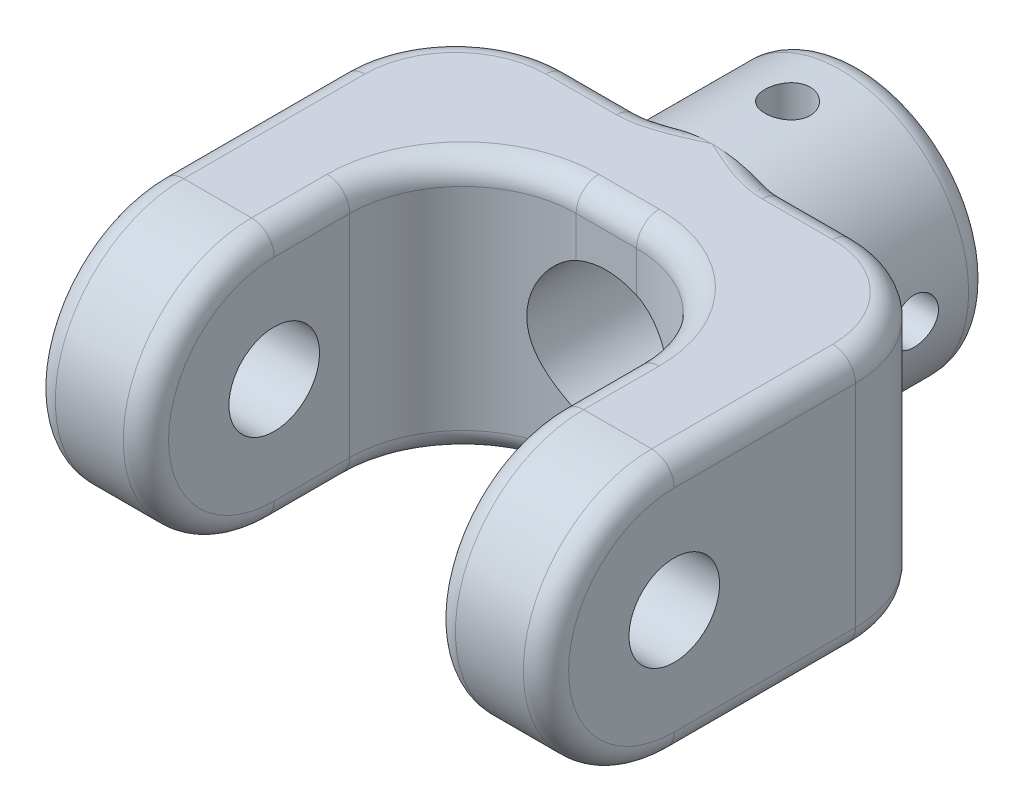
SolidWorks part; units mm, degrees
ref_plane "前视基准面" through (0, 0, 0) normal (0, 0, 1) x (1, 0, 0)
ref_plane "上视基准面" through (0, 0, 0) normal (0, 1, 0) x (1, 0, 0)
ref_plane "右视基准面" through (0, 0, 0) normal (1, 0, 0) x (0, 0, -1)
other "Configuration Table"
sketch "草图1" plane through (0, 0, 0) normal (0, 1, 0) x (1, 0, 0)
  line L0 (-768.9064, 0) -> (37676.4149, 0) construction
  line L1 (-17, 0) -> (17, 0)
  line L2 (17, 0) -> (17, -20)
  line L3 (0, -1000) -> (0, 49000) construction
  line L4 (17, -20) -> (19, -20)
  line L5 (34, -35) -> (34, -76)
  line L6 (34, -76) -> (19, -76)
  line L7 (19, -76) -> (19, -49)
  line L8 (-17, 0) -> (-17, -20)
  line L9 (-17, -20) -> (-19, -20)
  line L10 (-34, -76) -> (-19, -76)
  line L11 (-19, -76) -> (-19, -49)
  line L12 (-34, -35) -> (-34, -76)
  line L13 (-4, -34) -> (4, -34)
  arc A0 (19, -49) -> (4, -34) centre (4, -49) ccw
  arc A1 (-19, -49) -> (-4, -34) centre (-4, -49) cw
  arc A2 (34, -35) -> (19, -20) centre (19, -35) ccw
  arc A3 (-34, -35) -> (-19, -20) centre (-19, -35) cw
  point P6 (0, 0)
  dimension "D7" = 30
  dimension "D8" = 30
  dimension "D1" = 34
  dimension "D2" = 20
  dimension "D3" = 56
  dimension "D4" = 34
  dimension "D5" = 15
  dimension "D6" = 42
extrude "凸台-拉伸1" add sketch "草图1" along normal blind 34
sketch "草图3" plane through (0, 0, 0) normal (0, 0, 1) x (1, 0, 0)
  line L0 (-17, 34) -> (17, 0) construction
  line L5 (-17, 0) -> (17, 0)
  line L6 (-17, 34) -> (-17, 0)
  line L7 (17, 34) -> (-17, 34)
  line L8 (17, 0) -> (17, 34)
  line L9 (-17, 0) -> (17, 0)
  line L10 (-17, 34) -> (-17, 0)
  line L11 (17, 34) -> (-17, 34)
  line L12 (17, 0) -> (17, 34)
  circle A0 centre (0, 17) radius 17
  dimension "D1" = 0
extrude "切除-拉伸1" cut sketch "草图3" along normal up to surface (20 mm away) contours A0 L10 L9 | L0 L10 A0 | L11 L0 A0 | A0 L12 L11 | A0 L0 L12 | L0 A0 L9 region at (-10.9375, 32.468, 0) region at (-15.468, 27.9375, 0) region at (-13.2027, 3.7973, 0) region at (13.2027, 30.2027, 0) region at (15.468, 6.0625, 0) region at (10.9375, 1.532, 0) up to face at (18, 17, 20)
sketch "草图5" plane through (0, 0, 0) normal (0, 0, 1) x (1, 0, 0)
  circle A0 centre (0, 17) radius 9.5
  dimension "D1" = 19
extrude "切除-拉伸2" cut sketch "草图5" along normal through all contours A0
sketch "草图6" plane through (0, 0, 0) normal (1, 0, 0) x (0, 0, -1)
  line L4 (-76, 0) -> (-35, 0)
  line L5 (-35, 0) -> (-35, 34)
  line L6 (-35, 34) -> (-76, 34)
  line L7 (-76, 34) -> (-76, 0)
  line L8 (-76, 0) -> (-59, 0)
  line L10 (-59, 34) -> (-76, 34)
  line L11 (-76, 34) -> (-76, 0)
  arc A0 (-59, 34) -> (-59, 0) centre (-59, 17) ccw
  dimension "D1" = 0
extrude "切除-拉伸3" cut sketch "草图6" against normal through all and the other way through all contours A0 L10 L11 | A0 L11 L8 region at (0, 3.7973, 72.2027) region at (0, 30.2027, 72.2027)
sketch "草图7" plane through (0, 0, 0) normal (1, 0, 0) x (0, 0, -1)
  circle A0 centre (-59, 17) radius 6
  dimension "D1" = 12
extrude "切除-拉伸4" cut sketch "草图7" against normal through all and the other way through all
sketch "草图8" plane through (0, 0, 0) normal (0, 1, 0) x (1, 0, 0)
  line L0 (9.5, 0) -> (-9.5, 0) construction
  line L1 (-17, 0) -> (-17, -20) construction
  circle A0 centre (0, -10) radius 3
  dimension "D1" = 6
  dimension "D2" = 10
  dimension "D3" = 17
extrude "切除-拉伸5" cut sketch "草图8" along normal through all
sketch "草图9" plane through (0, 0, 0) normal (1, 0, 0) x (0, 0, -1)
  line L0 (0, 0) -> (0, 34) construction
  line L1 (-13, 34) -> (-20, 34) construction
  circle A0 centre (-10, 17) radius 3
  dimension "D1" = 6
  dimension "D2" = 10
  dimension "D3" = 17
extrude "切除-拉伸6" cut sketch "草图9" against normal through all and the other way through all
fillet "圆角1" radius 3 27 edges at (-19, 34, 54) (0, 34, 34) (-14.6066, 34, 38.3934) (-19, 17, 76) (-19, 0, 54) (-14.6066, 0, 38.3934) (0, 0, 34) (14.6066, 0, 38.3934) (19, 0, 54) (19, 17, 76) (19, 34, 54) (14.6066, 34, 38.3934) (34, 17, 76) (34, 34, 47) (34, 0, 47) (9.5, 0, 20) (-9.5, 0, 20) (29.6066, 0, 24.3934) (29.6066, 34, 24.3934) (9.5, 34, 20) (-9.5, 34, 20) (-29.6066, 34, 24.3934) (-34, 34, 47) (-34, 17, 76) (-29.6066, 0, 24.3934) (-34, 0, 47) (17, 17, 0)
